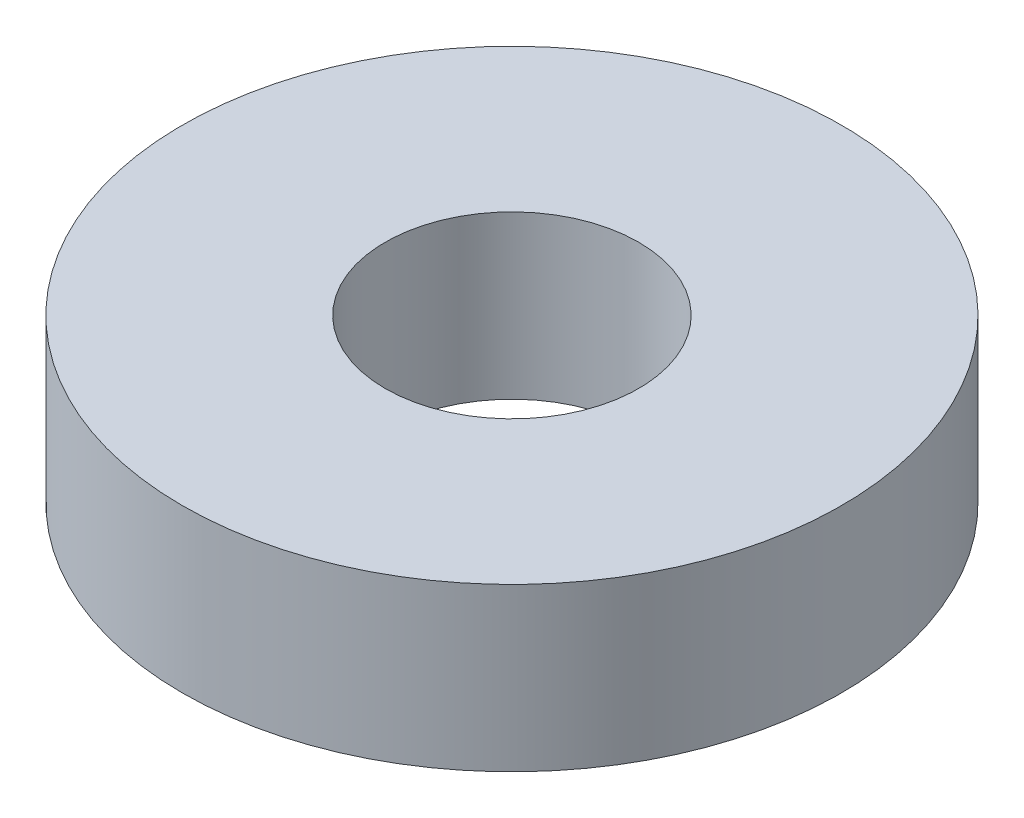
SolidWorks part; units mm, degrees
ref_plane "Front Plane" through (0, 0, 0) normal (0, 0, 1) x (1, 0, 0)
ref_plane "Top Plane" through (0, 0, 0) normal (0, 1, 0) x (1, 0, 0)
ref_plane "Right Plane" through (0, 0, 0) normal (1, 0, 0) x (0, 0, -1)
sketch "Sketch1" plane through (0, 0, 0) normal (0, 1, 0) x (1, 0, 0)
  circle A0 centre (0, 0) radius 32.5
  dimension "FLANGE_OD" = 65
extrude "Boss-Extrude1" add sketch "Sketch1" along normal blind 16
sketch "Sketch2" plane through (0, 0, 0) normal (0, 1, 0) x (1, 0, 0)
  circle A0 centre (0, 0) radius 12.5
  dimension "BORE_D" = 25
extrude "Cut-Extrude1" cut sketch "Sketch2" along normal through all
sketch "Sketch3" plane through (0, 16, 0) normal (0, 1, 0) x (1, 0, 0)
  circle A0 centre (0, 0) radius 8.7297 construction
  circle A1 centre (-8.7297, 0) radius 2.5616
  dimension "BOLT_D" = 5.1233
  dimension "BOLT_PCD" = 17.4595
extrude "Cut-Extrude2" cut sketch "Sketch3" against normal blind 12.3712 rebuild error yes
pattern_circular "CirPattern1" count 6 over 360 rebuild error yes
